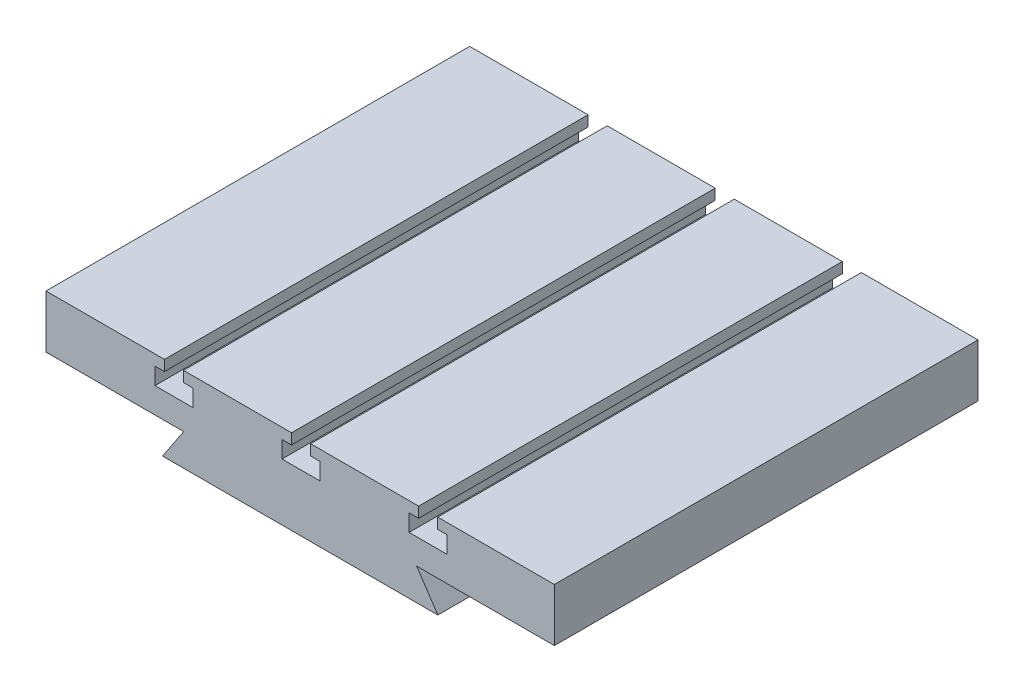
SolidWorks part; units mm, degrees
ref_plane "Спереди" through (0, 0, 0) normal (0, 0, 1) x (1, 0, 0)
ref_plane "Сверху" through (0, 0, 0) normal (0, 1, 0) x (1, 0, 0)
ref_plane "Справа" through (0, 0, 0) normal (1, 0, 0) x (0, 0, -1)
sketch "Эскиз1" plane through (0, 0, 0) normal (0, 0, 1) x (1, 0, 0)
  line L0 (0, 0) -> (65, 0)
  line L1 (65, 0) -> (55, 15)
  line L2 (55, 15) -> (120, 15)
  line L3 (120, 15) -> (120, 40)
  line L4 (120, 40) -> (0, 40)
  line L5 (0, 56.4782) -> (0, 0) construction
  line L6 (-120, 40) -> (0, 40)
  line L7 (-120, 15) -> (-120, 40)
  line L8 (-55, 15) -> (-120, 15)
  line L9 (-65, 0) -> (-55, 15)
  line L10 (0, 0) -> (-65, 0)
  line L11 (-75, 0) -> (75, 0) construction
  point P3 (0, 0)
  point P8 (0, 0)
  point P9 (0, 0)
  dimension "D1" = 25
  dimension "D2" = 65
  dimension "D3" = 120
extrude "Бобышка-Вытянуть1" add sketch "Эскиз1" along normal blind 200
sketch "Эскиз2" plane through (0, 0, 200) normal (0, 0, 1) x (1, 0, 0)
  line L0 (-8.5738, 27) -> (9.4262, 27)
  line L1 (9.4262, 27) -> (9.4262, 35)
  line L2 (9.4262, 35) -> (4.9262, 35)
  line L3 (4.9262, 35) -> (4.9262, 40)
  line L4 (120, 40) -> (-120, 40) construction
  line L5 (4.9262, 40) -> (-4.0738, 40)
  line L6 (-4.0738, 40) -> (-4.0738, 35)
  line L7 (-4.0738, 35) -> (-8.5738, 35)
  line L8 (-8.5738, 35) -> (-8.5738, 27)
  line L9 (51.4262, 27) -> (69.4262, 27)
  line L10 (69.4262, 27) -> (69.4262, 35)
  line L11 (69.4262, 35) -> (64.9262, 35)
  line L12 (64.9262, 35) -> (64.9262, 40)
  line L13 (64.9262, 40) -> (55.9262, 40)
  line L14 (55.9262, 40) -> (55.9262, 35)
  line L15 (55.9262, 35) -> (51.4262, 35)
  line L16 (51.4262, 35) -> (51.4262, 27)
  line L17 (-68.5738, 27) -> (-50.5738, 27)
  line L18 (-50.5738, 27) -> (-50.5738, 35)
  line L19 (-50.5738, 35) -> (-55.0738, 35)
  line L20 (-55.0738, 35) -> (-55.0738, 40)
  line L21 (-55.0738, 40) -> (-64.0738, 40)
  line L22 (-64.0738, 40) -> (-64.0738, 35)
  line L23 (-64.0738, 35) -> (-68.5738, 35)
  line L24 (-68.5738, 35) -> (-68.5738, 27)
  point P3 (0.4262, 27)
  point P15 (60.4262, 27)
  point P23 (-59.5738, 27)
  dimension "D1" = 18
  dimension "D2" = 9
  dimension "D3" = 5
  dimension "D4" = 8
  dimension "D5" = 2
  dimension "D6" = 2
extrude "Вырез-Вытянуть1" cut sketch "Эскиз2" against normal through all
